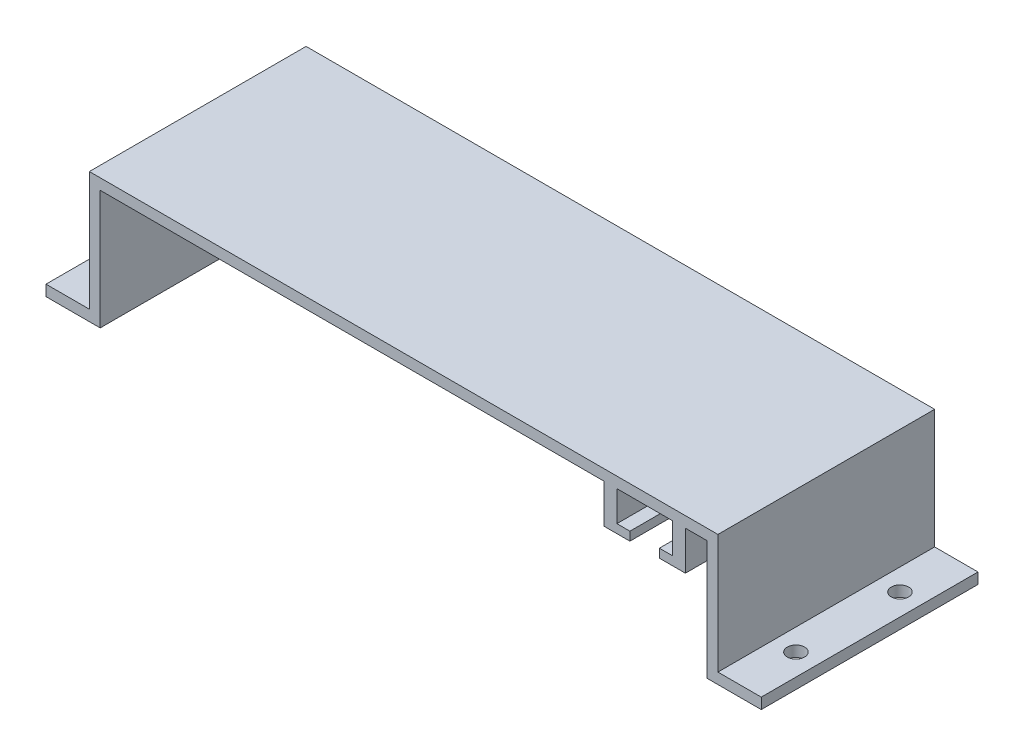
SolidWorks part; units mm, degrees
ref_plane "Front Plane" through (0, 0, 0) normal (0, 0, 1) x (1, 0, 0)
ref_plane "Top Plane" through (0, 0, 0) normal (0, 1, 0) x (1, 0, 0)
ref_plane "Right Plane" through (0, 0, 0) normal (1, 0, 0) x (0, 0, -1)
sketch "Sketch1" plane through (0, 0, 0) normal (0, 1, 0) x (1, 0, 0)
  line L1 (-88.9, 31.75) -> (88.9, 31.75)
  line L2 (-88.9, 31.75) -> (-88.9, -31.75)
  line L3 (-88.9, -31.75) -> (88.9, -31.75)
  line L4 (88.9, 31.75) -> (88.9, -31.75)
  line L5 (-88.9, 31.75) -> (88.9, -31.75) construction
  line L6 (-88.9, -31.75) -> (88.9, 31.75) construction
  point P0 (0, 0)
  dimension "D1" = 177.8
  dimension "D2" = 63.5
extrude "Boss-Extrude1" add sketch "Sketch1" along normal blind 3.175
sketch "Sketch3" plane through (0, 3.175, 0) normal (0, 1, 0) x (1, 0, 0)
  line L0 (-88.9, -31.75) -> (88.9, -31.75) construction
  line L1 (-88.9, 31.75) -> (-92.075, 31.75)
  line L2 (-88.9, 31.75) -> (-88.9, -31.75)
  line L3 (-88.9, -31.75) -> (-92.075, -31.75)
  line L4 (-92.075, 31.75) -> (-92.075, -31.75)
  line L5 (0, -55) -> (0, 55) construction
  line L6 (88.9, -31.75) -> (92.075, -31.75)
  line L7 (92.075, 31.75) -> (92.075, -31.75)
  line L8 (88.9, 31.75) -> (92.075, 31.75)
  line L9 (88.9, 31.75) -> (88.9, -31.75)
  dimension "D1" = 3.175
extrude "Boss-Extrude2" add sketch "Sketch3" against normal blind 38.1
sketch "Sketch4" plane through (92.075, 0, 0) normal (1, 0, 0) x (0, 0, -1)
  line L0 (31.75, -34.925) -> (31.75, 3.175) construction
  line L1 (-31.75, -34.925) -> (31.75, -34.925)
  line L2 (-31.75, -34.925) -> (-31.75, -31.75)
  line L3 (-31.75, -31.75) -> (31.75, -31.75)
  line L4 (31.75, -34.925) -> (31.75, -31.75)
  dimension "D1" = 3.175
extrude "Boss-Extrude3" add sketch "Sketch4" along normal blind 12.7
sketch "Sketch5" plane through (0, -34.925, 0) normal (0, -1, 0) x (1, 0, 0)
  line L1 (104.775, -31.75) -> (88.9, -31.75) construction
  line L3 (88.9, 0) -> (104.775, 0) construction
  line L4 (88.9, 31.75) -> (88.9, -31.75) construction
  line L5 (104.775, 31.75) -> (104.775, -31.75) construction
  circle A0 centre (98.425, -15.24) radius 2.54
  circle A1 centre (98.425, 15.24) radius 2.54
  dimension "D1" = 5.08
  dimension "D2" = 6.35
  dimension "D3" = 16.51
extrude "Cut-Extrude1" cut sketch "Sketch5" against normal blind 12.7
mirror "Mirror1" about plane through (0, 0, 0) normal (1, 0, 0) of "Boss-Extrude3", "Cut-Extrude1"
sketch "Sketch6" plane through (0, 0, 31.75) normal (0, 0, 1) x (1, 0, 0)
  line L0 (58.674, 0) -> (58.674, -11.43)
  line L1 (-88.9, 0) -> (88.9, 0) construction
  line L2 (58.674, -11.43) -> (66.294, -11.43)
  line L3 (66.294, -11.43) -> (66.294, -8.89)
  line L4 (66.294, -8.89) -> (62.484, -8.89)
  line L5 (62.484, -8.89) -> (62.484, 0)
  line L6 (82.55, 0) -> (82.55, -11.43)
  line L7 (82.55, -11.43) -> (74.93, -11.43)
  line L8 (74.93, -11.43) -> (74.93, -8.89)
  line L9 (74.93, -8.89) -> (78.74, -8.89)
  line L10 (78.74, -8.89) -> (78.74, 0)
  line L11 (-88.9, -34.925) -> (-88.9, 0) construction
  line L12 (82.55, 0) -> (78.74, 0)
  line L13 (62.484, 0) -> (58.674, 0)
  dimension "D1" = 11.43
  dimension "D2" = 2.54
  dimension "D3" = 3.81
  dimension "D4" = 3.81
  dimension "D5" = 167.64
  dimension "D6" = 16.256
extrude "Boss-Extrude4" add sketch "Sketch6" against normal up to surface (63.5 mm away) up to face at (0, -21.6958, -31.75)
